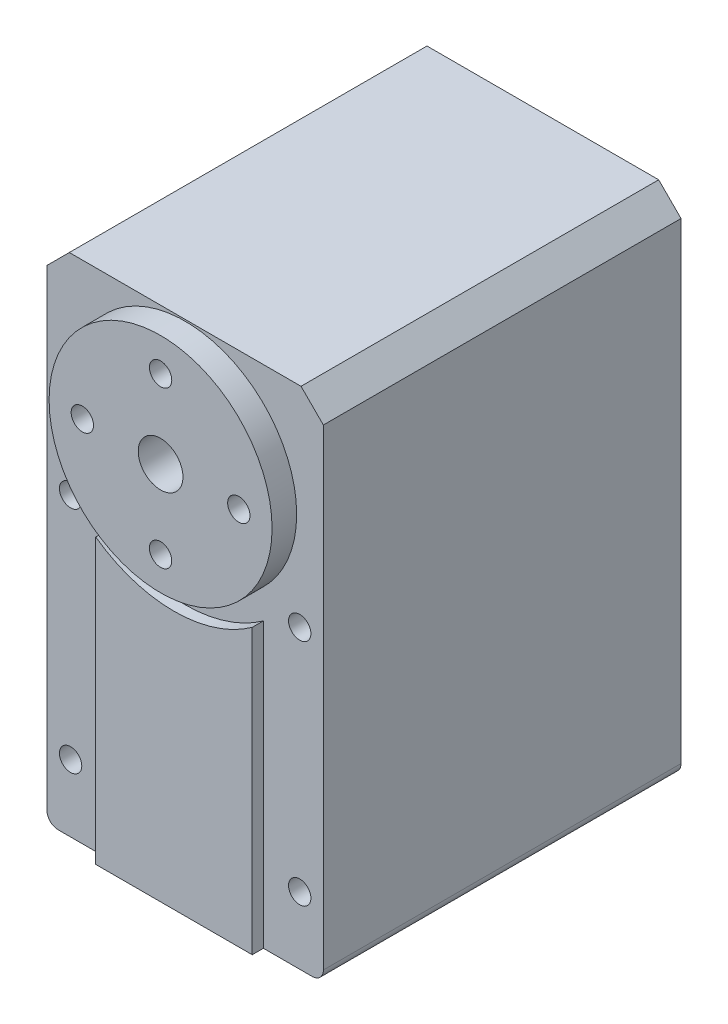
SolidWorks part; units mm, degrees
ref_plane "정면" through (0, 0, 0) normal (0, 0, 1) x (1, 0, 0)
ref_plane "윗면" through (0, 0, 0) normal (0, 1, 0) x (1, 0, 0)
ref_plane "우측면" through (0, 0, 0) normal (1, 0, 0) x (0, 0, -1)
sketch "스케치1" plane through (0, 0, 0) normal (0, 0, 1) x (1, 0, 0)
  line L1 (-12.365, 22.615) -> (12.365, 22.615)
  line L2 (-12.365, 22.615) -> (-12.365, -22.615)
  line L3 (-12.365, -22.615) -> (12.365, -22.615)
  line L4 (12.365, 22.615) -> (12.365, -22.615)
  line L5 (-12.365, 22.615) -> (12.365, -22.615) construction
  line L6 (-12.365, -22.615) -> (12.365, 22.615) construction
  point P0 (0, 0)
  dimension "D1" = 24.73
  dimension "D2" = 45.23
extrude "보스-돌출1" add sketch "스케치1" along normal blind 32
chamfer "모따기1" distance 2 angle 45 2 edges at (-12.365, 22.615, 16) (12.365, 22.615, 16)
sketch "스케치2" plane through (0, 0, 32) normal (0, 0, 1) x (1, 0, 0)
  line L0 (-12.365, -22.615) -> (12.365, -22.615) construction
  line L1 (-7, -22.615) -> (7, -22.615)
  line L2 (-7, -22.615) -> (-7, 2.7532)
  line L4 (7, -22.615) -> (7, 2.7532)
  arc A0 (-7, 2.7532) -> (7, 2.7532) centre (0, 12.5) ccw
  dimension "D4" = 24
  dimension "D1" = 14
  dimension "D2" = 7
  dimension "D3" = 12.5
extrude "보스-돌출2" add sketch "스케치2" along normal blind 1
sketch "스케치3" plane through (0, 0, 32) normal (0, 0, 1) x (1, 0, 0)
  line L0 (7, -22.615) -> (12.365, -22.615) construction
  line L1 (-10.25, -16.615) -> (10.25, -16.615) construction
  line L2 (-10.25, -16.615) -> (-10.25, 3.885) construction
  line L3 (-10.25, 3.885) -> (10.25, 3.885) construction
  line L4 (10.25, -16.615) -> (10.25, 3.885) construction
  circle A0 centre (-10.25, 3.885) radius 1
  circle A1 centre (-10.25, -16.615) radius 1
  circle A2 centre (10.25, -16.615) radius 1
  circle A3 centre (10.25, 3.885) radius 1
  dimension "D5" = 2
  dimension "D1" = 20.5
  dimension "D2" = 20.5
  dimension "D3" = 6
  dimension "D4" = 10.25
extrude "컷-돌출1" cut sketch "스케치3" against normal blind 4
sketch "스케치4" plane through (0, 0, 32) normal (0, 0, 1) x (1, 0, 0)
  circle A0 centre (0, 12.5) radius 9.975
  dimension "D1" = 12.5
  dimension "D2" = 19.95
extrude "보스-돌출3" add sketch "스케치4" along normal blind 2.2
sketch "스케치5" plane through (0, 0, 34.2) normal (0, 0, 1) x (1, 0, 0)
  circle A0 centre (0, 12.5) radius 7 construction
  circle A5 centre (0, 12.5) radius 2
  circle A6 centre (0, 19.5) radius 1
  circle A7 centre (7, 12.5) radius 1
  circle A8 centre (0, 12.5) radius 7 construction
  circle A9 centre (0, 5.5) radius 1
  circle A10 centre (0, 12.5) radius 7 construction
  circle A11 centre (-7, 12.5) radius 1
  circle A12 centre (0, 12.5) radius 7 construction
  point P18 (0, 12.5)
  dimension "D1" = 14
  dimension "D2" = 2
  dimension "D3" = 4
  dimension "D4" = 4
extrude "컷-돌출2" cut sketch "스케치5" against normal blind 3
sketch "스케치6" plane through (0, 0, 0) normal (0, 0, -1) x (-1, 0, 0)
  line L0 (-12.365, -22.615) -> (-12.365, 20.615) construction
  line L1 (-10.165, -18.115) -> (10.165, -18.115)
  line L2 (-10.165, -18.115) -> (-10.165, -6.115)
  line L3 (-10.165, -6.115) -> (10.165, -6.115)
  line L4 (10.165, -18.115) -> (10.165, -6.115)
  line L5 (12.365, 20.615) -> (12.365, -22.615) construction
  line L6 (12.365, -22.615) -> (-12.365, -22.615) construction
  dimension "D1" = 2.2
  dimension "D2" = 2.2
  dimension "D3" = 4.5
  dimension "D4" = 12
extrude "보스-돌출4" add sketch "스케치6" along normal blind 2
chamfer "모따기2" distance 2 angle 45 1 edges at (0, -6.115, -2)
sketch "스케치7" plane through (0, 0, 0) normal (0, 0, -1) x (-1, 0, 0)
  line L0 (12.365, 20.615) -> (12.365, -22.615) construction
  line L1 (11.165, -6.115) -> (-11.165, -6.115)
  line L2 (11.165, -6.115) -> (11.165, -1.115)
  line L3 (11.165, -1.115) -> (-11.165, -1.115)
  line L4 (-11.165, -6.115) -> (-11.165, -1.115)
  line L5 (-12.365, -22.615) -> (-12.365, 20.615) construction
  line L6 (10.165, -6.115) -> (-10.165, -6.115) construction
  dimension "D1" = 1.2
  dimension "D2" = 1.2
  dimension "D3" = 5
extrude "컷-돌출3" cut sketch "스케치7" against normal blind 2
sketch "스케치8" plane through (0, 0, 0) normal (0, 0, -1) x (-1, 0, 0)
  circle A0 centre (0, 12.5) radius 3
  dimension "D1" = 12.5
  dimension "D2" = 6
extrude "보스-돌출5" add sketch "스케치8" along normal blind 4.1
sketch "스케치9" plane through (0, 0, 0) normal (0, 0, -1) x (-1, 0, 0)
  line L0 (12.365, -22.615) -> (-12.365, -22.615) construction
  line L1 (-10.25, -20.615) -> (10.25, -20.615) construction
  line L2 (-10.25, -20.615) -> (-10.25, 3.885) construction
  line L3 (-10.25, 3.885) -> (10.25, 3.885) construction
  line L4 (10.25, -20.615) -> (10.25, 3.885) construction
  circle A0 centre (-10.25, 3.885) radius 1
  circle A1 centre (10.25, 3.885) radius 1
  circle A2 centre (-10.25, -20.615) radius 1
  circle A3 centre (10.25, -20.615) radius 1
  dimension "D5" = 2
  dimension "D1" = 20.5
  dimension "D2" = 24.5
  dimension "D3" = 10.25
  dimension "D4" = 2
extrude "컷-돌출4" cut sketch "스케치9" against normal blind 4
fillet "필렛1" radius 1 2 edges at (-12.365, -22.615, 16) (12.365, -22.615, 16)
